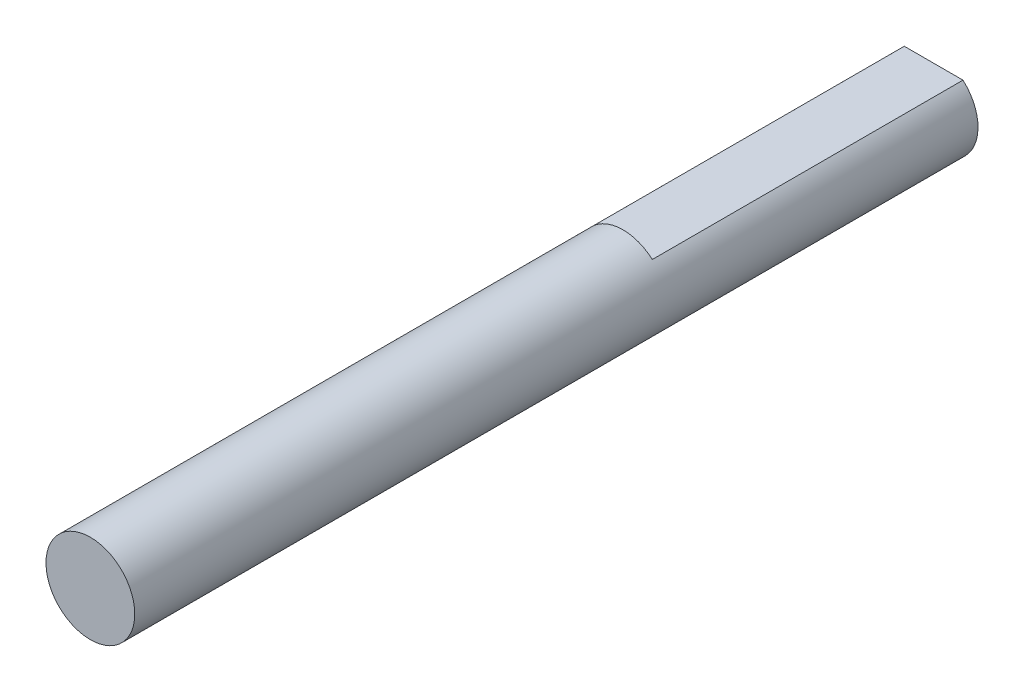
SolidWorks part; units mm, degrees
ref_plane "Ön Düzlem" through (0, 0, 0) normal (0, 0, 1) x (1, 0, 0)
ref_plane "Üst Düzlem" through (0, 0, 0) normal (0, 1, 0) x (1, 0, 0)
ref_plane "Sağ Düzlem" through (0, 0, 0) normal (1, 0, 0) x (0, 0, -1)
sketch "Sketch1" plane through (0, 0, 0) normal (0, 0, 1) x (1, 0, 0)
  line L0 (-1.3229, 1.5) -> (1.3229, 1.5)
  circle A0 centre (0, 0) radius 2
  point P5 (0, 1.5)
  dimension "D1" = 4
  dimension "D2" = 1.5
extrude "Boss-Extrude2" add sketch "Sketch1" along normal blind 24 contours A0
extrude "Boss-Extrude3" add sketch "Sketch1<4>" against normal blind 14 contours L0 A0 region at (0, -0.1324, 0)
sketch "Sketch1<4>" plane through (0, 0, 0) normal (0, 0, 1) x (1, 0, 0) same geometry as "Sketch1"
